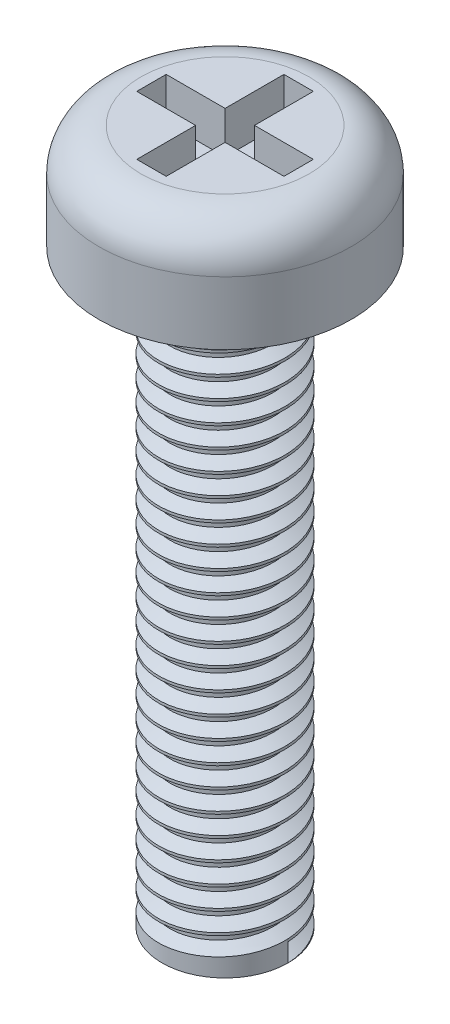
SolidWorks part; units mm, degrees
ref_plane "Front Plane" through (0, 0, 0) normal (0, 0, 1) x (1, 0, 0)
ref_plane "Top Plane" through (0, 0, 0) normal (0, 1, 0) x (1, 0, 0)
ref_plane "Right Plane" through (0, 0, 0) normal (1, 0, 0) x (0, 0, -1)
sketch "Sketch1" plane through (0, 0, 0) normal (0, 1, 0) x (1, 0, 0)
  circle A0 centre (0, 0) radius 3
  dimension "D1" = 6
extrude "Boss-Extrude1" add sketch "Sketch1" along normal blind 2.5
fillet "Fillet1" radius 1 1 edges at (0, 2.5, 3)
sketch "Sketch2" plane through (0, 2.5, 0) normal (0, 1, 0) x (1, 0, 0)
  line L0 (-1.75, 0.35) -> (-0.35, 0.35)
  line L1 (-0.35, 1.75) -> (0.35, 1.75)
  line L3 (-0.35, -1.75) -> (0.35, -1.75)
  line L5 (0, -1.75) -> (0, 1.75) construction
  line L6 (-0.35, 0) -> (0.35, 0) construction
  line L8 (1.75, 0.35) -> (1.75, -0.35)
  line L10 (-1.75, 0.35) -> (-1.75, -0.35)
  line L11 (0, -0.35) -> (0, 0.35) construction
  line L12 (1.75, 0) -> (-1.75, 0) construction
  line L13 (-0.35, 0.35) -> (-0.35, 1.75)
  line L14 (0.35, 1.75) -> (0.35, 0.35)
  line L15 (0.35, 0.35) -> (1.75, 0.35)
  line L16 (1.75, -0.35) -> (0.35, -0.35)
  line L17 (0.35, -0.35) -> (0.35, -1.75)
  line L18 (-0.35, -1.75) -> (-0.35, -0.35)
  line L19 (-0.35, -0.35) -> (-1.75, -0.35)
  point P0 (0, 0)
  point P4 (0, 0)
  dimension "D1" = 3.5
  dimension "D2" = 0.7
  dimension "D3" = 3.5
  dimension "D4" = 0.7
extrude "Cut-Extrude1" cut sketch "Sketch2" against normal blind 1
sketch "Sketch3" plane through (0, 0, 0) normal (0, -1, 0) x (1, 0, 0)
  circle A0 centre (0, 0) radius 1.5
  dimension "D1" = 3
extrude "Boss-Extrude2" add sketch "Sketch3" along normal blind 14
thread "Thread1" pitch 0.5 method cut profile "Thread Profile1" start angle 0, offset 0, length 13, pitch 0.5, diameter 3
ref_plane "Plane1" through (1.5, -14, 0) normal (0, 0, 1) x (1, 0, 0)
sketch "Thread Profile1" plane through (1.5, -14, 0) normal (0, 0, 1) x (1, 0, 0)
  line L0 (0, 0) -> (0, 0.5) construction
  line L11 (0, 0) -> (0, 0.4375)
  line L12 (0, 0.4375) -> (-0.2706, 0.2812)
  line L13 (-0.2706, 0.2812) -> (-0.2706, 0.1562)
  line L15 (-0.2706, 0.1562) -> (0, 0)
  line L17 (-0.2706, 0.2187) -> (0, 0.2187) construction
  point P2 (0, 0)
  dimension "Pitch" = 0.5
  dimension "Profile_Angle" = 60
  dimension "Profile_Land" = 0.125
  dimension "Profile_Height" = 0.2706
